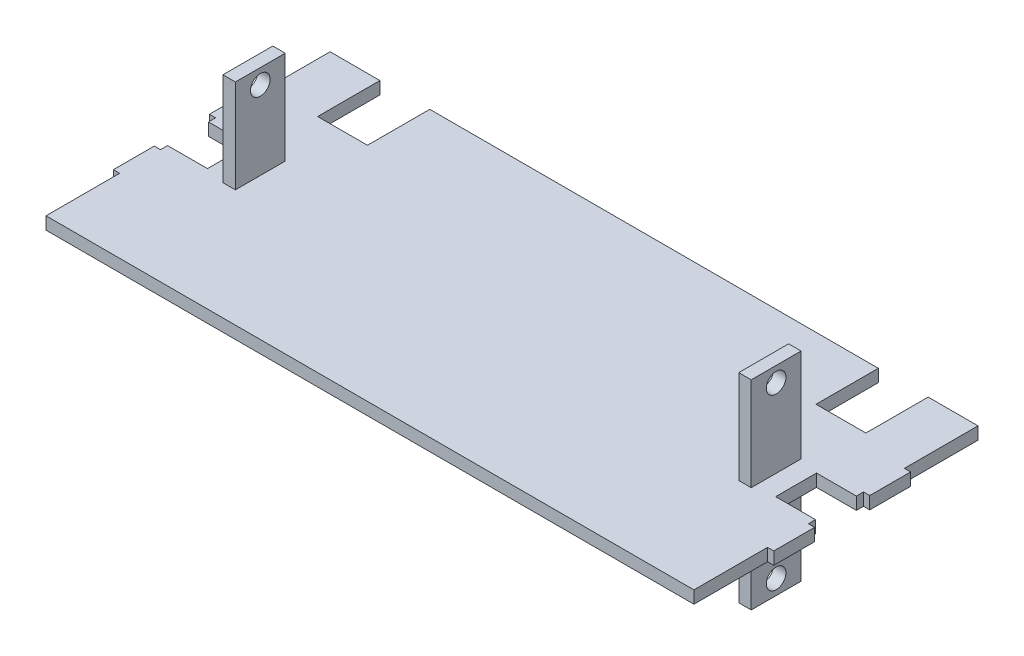
SolidWorks part; units mm, degrees
ref_plane "Front Plane" through (0, 0, 0) normal (0, 0, 1) x (1, 0, 0)
ref_plane "Top Plane" through (0, 0, 0) normal (0, 1, 0) x (1, 0, 0)
ref_plane "Right Plane" through (0, 0, 0) normal (1, 0, 0) x (0, 0, -1)
sketch "Sketch1" plane through (0, 0, 0) normal (0, 1, 0) x (1, 0, 0)
  line L0 (0, 72.39) -> (0, -72.39) construction
  line L1 (165.1, -72.39) -> (-165.1, -72.39)
  line L2 (165.1, -72.39) -> (165.1, -34.8747)
  line L3 (165.1, 72.39) -> (139.7, 72.39)
  line L4 (-165.1, -72.39) -> (-165.1, -34.8747)
  line L5 (165.1, -72.39) -> (-165.1, 72.39) construction
  line L6 (165.1, 72.39) -> (-165.1, -72.39) construction
  line L7 (165.1, 10.414) -> (144.78, 10.414)
  line L9 (165.1, -10.414) -> (144.78, -10.414)
  line L10 (144.78, 10.414) -> (144.78, -10.414)
  line L11 (-139.7, 72.39) -> (-165.1, 72.39)
  line L13 (-165.1, -10.414) -> (-144.78, -10.414)
  line L14 (-144.78, 10.414) -> (-144.78, -10.414)
  line L15 (-165.1, 10.414) -> (-144.78, 10.414)
  line L17 (-127, 0) -> (127, 0) construction
  line L18 (-165.1, 14.0467) -> (-168.275, 14.0467)
  line L20 (-165.1, 34.8747) -> (-168.275, 34.8747)
  line L21 (-168.275, 14.0467) -> (-168.275, 34.8747)
  line L22 (-165.1, -34.8747) -> (-168.275, -34.8747)
  line L23 (-168.275, -14.0467) -> (-168.275, -34.8747)
  line L24 (-165.1, -14.0467) -> (-168.275, -14.0467)
  line L27 (165.1, -14.0467) -> (168.275, -14.0467)
  line L28 (168.275, -14.0467) -> (168.275, -34.8747)
  line L29 (165.1, -34.8747) -> (168.275, -34.8747)
  line L30 (165.1, 34.8747) -> (168.275, 34.8747)
  line L31 (168.275, 14.0467) -> (168.275, 34.8747)
  line L32 (165.1, 14.0467) -> (168.275, 14.0467)
  line L34 (-165.1, 34.8747) -> (-165.1, 72.39)
  line L35 (-165.1, -14.0467) -> (-165.1, -10.414)
  line L36 (165.1, 34.8747) -> (165.1, 72.39)
  line L37 (165.1, -14.0467) -> (165.1, -10.414)
  line L38 (-165.1, 10.414) -> (-165.1, 14.0467)
  line L39 (165.1, 10.414) -> (165.1, 14.0467)
  line L40 (-139.7, 72.39) -> (-139.7, 40.64)
  line L41 (-139.7, 40.64) -> (-114.3, 40.64)
  line L42 (-114.3, 72.39) -> (-114.3, 40.64)
  line L44 (114.3, 72.39) -> (114.3, 40.64)
  line L45 (114.3, 40.64) -> (139.7, 40.64)
  line L46 (139.7, 72.39) -> (139.7, 40.64)
  line L47 (114.3, 72.39) -> (-114.3, 72.39)
  point P0 (0, 0)
  point P6 (127, 0)
  dimension "D1" = 330.2
  dimension "D2" = 144.78
  dimension "D3" = 20.828
  dimension "D5" = 3.175
  dimension "D6" = 20.828
  dimension "D4" = 20.32
  dimension "D7" = 31.75
  dimension "D8" = 25.4
  dimension "D9" = 25.4
  dimension "D10" = 31.75
  dimension "D12" = 25.4
  dimension "D11" = 25.4
extrude "Boss-Extrude1" add sketch "Sketch1" along normal mid plane 6.35
sketch "Sketch2" plane through (0, 0, 0) normal (0, 1, 0) x (1, 0, 0)
  line L0 (-144.78, 10.414) -> (-144.78, -10.414) construction
  line L1 (128.27, -12.7) -> (134.62, -12.7)
  line L2 (128.27, -12.7) -> (128.27, 12.7)
  line L3 (128.27, 12.7) -> (134.62, 12.7)
  line L4 (134.62, -12.7) -> (134.62, 12.7)
  line L5 (128.27, -12.7) -> (134.62, 12.7) construction
  line L6 (128.27, 12.7) -> (134.62, -12.7) construction
  line L9 (-128.27, -12.7) -> (-128.27, 12.7)
  line L10 (-128.27, 12.7) -> (-134.62, 12.7)
  line L11 (-134.62, -12.7) -> (-134.62, 12.7)
  line L12 (-128.27, -12.7) -> (-134.62, -12.7)
  line L13 (144.78, -10.414) -> (144.78, 10.414) construction
  point P0 (131.445, 0)
  point P10 (144.78, 0)
  dimension "D1" = 10.16
  dimension "D2" = 10.16
  dimension "D3" = 25.4
  dimension "D4" = 25.4
  dimension "D5" = 6.35
  dimension "D6" = 6.35
  dimension "D7" = 6.35
extrude "Boss-Extrude2" add sketch "Sketch2" along normal mid plane 101.6
sketch "Sketch3" plane through (-134.62, 0, 0) normal (-1, 0, 0) x (0, 0, 1)
  line L0 (-12.7, 50.8) -> (12.7, 50.8) construction
  line L1 (-12.7, -50.8) -> (12.7, -50.8) construction
  circle A0 centre (0, 43.18) radius 5.0038
  circle A1 centre (0, -43.18) radius 5.0038
  point P4 (0, 50.8)
  point P7 (0, 0)
  point P10 (0, 0)
  dimension "D1" = 10.0076
  dimension "D2" = 10.0076
  dimension "D3" = 7.62
  dimension "D4" = 7.62
  dimension "D5" = 86.36
extrude "Cut-Extrude1" cut sketch "Sketch3" against normal through all both and the other way through all
equation "\"length\"=13"
equation "\"width\"= 5.7"
equation "\"height\"= 0.25"
equation "\"D1@Sketch1\"=\"length\""
equation "\"D2@Sketch1\"=\"width\""
equation "\"eyebolt width\"= 0.82"
equation "\"eyebolt length\"= 0.8"
equation "\"D3@Sketch1\"=\"eyebolt width\""
equation "\"D4@Sketch1\"=\"eyebolt length\""
equation "\"lead screw holder height\"= 2.76"
equation "\"lead screw diameter\"=0.394"
equation "\"D1@Sketch3\"=\"lead screw diameter\""
equation "\"distance from holders to board\"=0.4"
equation "\"D2@Sketch3\"=\"lead screw diameter\""
equation "\"lead_screw_dist\"=3.4"
equation "\"D5@Sketch3\"=\"lead_screw_dist\""
